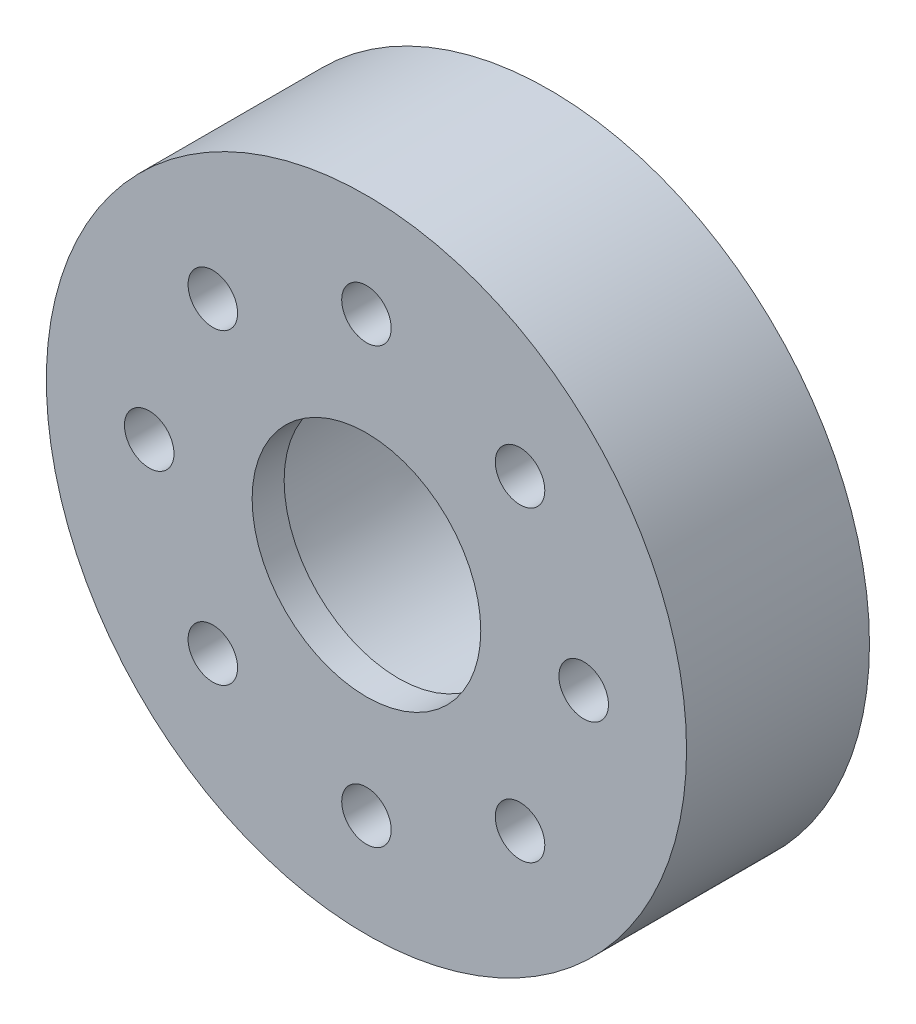
SolidWorks part; units mm, degrees
ref_plane "Front Plane" through (0, 0, 0) normal (0, 0, 1) x (1, 0, 0)
ref_plane "Top Plane" through (0, 0, 0) normal (0, 1, 0) x (1, 0, 0)
ref_plane "Right Plane" through (0, 0, 0) normal (1, 0, 0) x (0, 0, -1)
sketch "Sketch1" plane through (0, 0, 0) normal (0, 0, 1) x (1, 0, 0)
  circle A0 centre (0, 0) radius 35.56
  dimension "D1" = 71.12
extrude "Boss-Extrude1" add sketch "Sketch1" along normal blind 20.32
sketch "Sketch5" plane through (0, 0, 0) normal (0, 0, -1) x (-1, 0, 0)
  point P0 (0, 0)
sketch "Sketch6" plane through (0, 0, 0) normal (0, 0, -1) x (-1, 0, 0)
  circle A0 centre (0, 0) radius 29.21 construction
  circle A1 centre (0, 0) radius 24.13 construction
  point P5 (0, 24.13)
  dimension "D1" = 58.42
  dimension "D2" = 5.08
hole_wizard "1 NPT Tapped Hole2" positions "Sketch5" profile "Sketch7" size "1" standard "ANSI Inch" end condition up to next
sketch "Sketch7" plane through (0, 0, 0) normal (1, 0, 0) x (0, 1, 0)
  line L0 (0, 0) -> (0, 20.32)
  line L1 (0, 20.32) -> (14.4907, 20.32)
  line L2 (-15.228, 16.764) -> (-15.7299, 0) construction
  line L3 (14.4907, 20.32) -> (14.4907, 16.764)
  line L4 (14.4907, 16.764) -> (15.228, 16.764)
  line L5 (15.228, 16.764) -> (15.7299, 0)
  line L7 (15.7299, 0) -> (0, 0)
  line L8 (0, -6.35) -> (0, 107.95) construction
  line L11 (-14.4907, 16.764) -> (-15.228, 16.764) construction
  dimension "Thru Tap Drill Dia." = 28.9814
  dimension "Thru Tap Drill Depth" = 20.32
  dimension "Thread Dia." = 31.4598
  dimension "Thread Angle" = 3.43
  dimension "Thread Depth" = 16.764
cosmetic thread "Hole Thread1" parameters "D1"=16.764, "D2"=33.3988
hole_wizard "M5 Clearance Hole1" positions "Sketch6" profile "Sketch8" hole size "M5" standard "ANSI Metric" end condition up to next
sketch "Sketch8" plane through (0, 24.13, 0) normal (1, 0, 0) x (0, 1, 0)
  line L0 (0, 0) -> (0, 20.32)
  line L1 (0, 20.32) -> (2.75, 20.32)
  line L2 (2.75, 20.32) -> (2.75, 0)
  line L5 (2.75, 0) -> (0, 0)
  line L11 (0, -6.35) -> (0, 107.95) construction
  dimension "Thru Hole Dia." = 5.5
  dimension "Thru Hole Depth" = 20.32
pattern_circular "CirPattern1" count 8 every 45 about axis through (0, 0, 0) along (0, 0, -1) of "M5 Clearance Hole1"
sketch "Sketch9" plane through (0, 0, 20.32) normal (0, 0, 1) x (1, 0, 0)
  circle A0 centre (0, 0) radius 12.7
  circle A1 centre (0, 0) radius 14.4907 construction
  circle A2 centre (0, 0) radius 14.4907
  dimension "D1" = 25.4
extrude "Boss-Extrude2" add sketch "Sketch9" against normal up to surface (3.556 mm away) up to face at (-14.4907, 0, 16.764)
equation "\"cavity_depth\"=0.031in"
equation "\"Cavity_width\"=0.031in"
equation "\"tooth_width\"=0.01in"
equation "\"Flange_OD\"=2.3in"
equation "\"fitting_OD\"= 1.3in"
equation "\"plate_thick\"= .8in"
equation "\"D1@Boss-Extrude1\"=\"plate_thick\""
equation "\"D1@Sketch6\"=\"Flange_OD\""
equation "\"D1@Sketch1\"=\"IPS_flange_radius\"*2"
equation "\"bearing_radius\"= 0.629921"
equation "\"bearing_width\"=0.393701"
equation "\"kero_radius\"=0.334in"
equation "\"lox_radius\"=0.23622in"
equation "\"seal_step\"=0.01in"
equation "\"purge_length\"=0.04in"
equation "\"insert_radius\" = 0.6in"
equation "\"recycle_groove width\" = 0.06in"
equation "\"recycle_groove_depth\" = 0.06in"
equation "\"N2_purge_width\"= .06in"
equation "\"N2_purge_depth\"= .06in"
equation "\"drain_width\"= .06in"
equation "\"drain_depth\"= .06in"
equation "\"radial_clearance\"= .002in"
equation "\"IPS_flange_width\"= .25in"
equation "\"IPS_flange_radius\" = 1.4in"
equation "\"IPS_LOX_male_radius\"= .9in"
equation "\"IPS_Kero_male_radius\" = .9in"
equation "\"IPS_radius\"= .95in"
equation "\"InsertLength\"= 1in"
